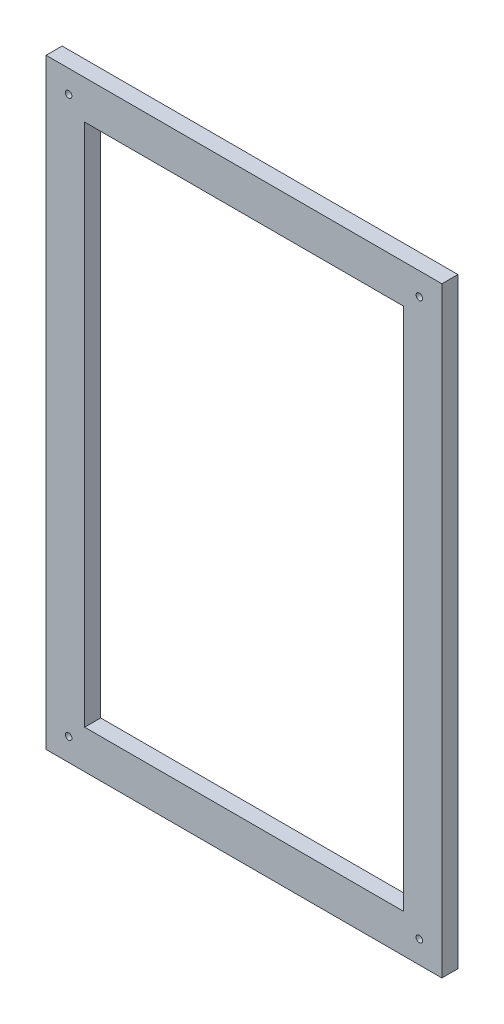
SolidWorks part; units mm, degrees
ref_plane "Front Plane" through (0, 0, 0) normal (0, 0, 1) x (1, 0, 0)
ref_plane "Top Plane" through (0, 0, 0) normal (0, 1, 0) x (1, 0, 0)
ref_plane "Right Plane" through (0, 0, 0) normal (1, 0, 0) x (0, 0, -1)
sketch "Sketch1" plane through (0, 0, 0) normal (0, 0, 1) x (1, 0, 0)
  line L1 (0, 0) -> (395, 0)
  line L2 (0, 0) -> (0, 600)
  line L3 (0, 600) -> (395, 600)
  line L4 (395, 0) -> (395, 600)
  dimension "D1" = 600
  dimension "D2" = 395
extrude "Base" add sketch "Sketch1" along normal blind 16
sketch "Sketch2" plane through (0, 0, 16) normal (0, 0, 1) x (1, 0, 0)
  line L0 (197.5, 600) -> (197.5, 0) construction
  line L1 (22.5, 577.5) -> (0, 577.5) construction
  line L2 (0, 600) -> (0, 0) construction
  line L3 (395, 600) -> (0, 600) construction
  line L4 (22.5, 577.5) -> (22.5, 600) construction
  line L6 (0, 0) -> (395, 0) construction
  line L8 (395, 300) -> (0, 300) construction
  line L9 (395, 0) -> (395, 600) construction
  line L10 (0, 600) -> (0, 0) construction
  circle A0 centre (22.5, 577.5) radius 3.25
  circle A1 centre (372.5, 577.5) radius 3.25
  circle A2 centre (372.5, 22.5) radius 3.25
  circle A3 centre (22.5, 22.5) radius 3.25
  dimension "D1" = 6.5
  dimension "D2" = 350
extrude "Mounting holes" cut sketch "Sketch2" against normal through all
sketch "Sketch3" plane through (0, 0, 0) normal (0, 0, -1) x (-1, 0, 0)
  line L0 (-395, 600) -> (0, 0) construction
  line L1 (-395, 0) -> (0, 600) construction
  line L2 (-395, 0) -> (-395, 600) construction
  line L3 (-356.5, 38.5) -> (-38.5, 38.5)
  line L4 (-356.5, 38.5) -> (-356.5, 561.5)
  line L5 (-356.5, 561.5) -> (-38.5, 561.5)
  line L6 (-38.5, 38.5) -> (-38.5, 561.5)
  line L7 (-356.5, 38.5) -> (-38.5, 561.5) construction
  line L8 (-356.5, 561.5) -> (-38.5, 38.5) construction
  line L9 (-356.5, 300) -> (-395, 300) construction
  line L10 (-197.5, 561.5) -> (-197.5, 600) construction
  line L11 (-395, 600) -> (0, 600) construction
  point P8 (-197.5, 300)
  dimension "D1" = 38.5
extrude "Center hole" cut sketch "Sketch3" against normal up to next
sketch "Sketch4" [suppressed] plane through (0, 0, 0) normal (0, 0, -1) x (-1, 0, 0)
  line L0 (-197.5, 600) -> (-197.5, 0) construction
  line L1 (-395, 600) -> (0, 600) construction
  line L2 (0, 0) -> (-395, 0) construction
  line L3 (-395, 40) -> (0, 40) construction
  line L4 (-395, 0) -> (-395, 600) construction
  line L5 (0, 600) -> (0, 0) construction
  line L6 (-197.5, 50) -> (0, 50) construction
  circle A0 centre (-197.5, 57.5) radius 7.5
  dimension "D3" = 15
  dimension "D1" = 40
  dimension "D2" = 10
extrude "Tap hole" [suppressed] cut sketch "Sketch4" against normal up to next
equation "\"D2@Sketch2\"=50*7"
equation "\"D1@Sketch3\"=2*19.25"
